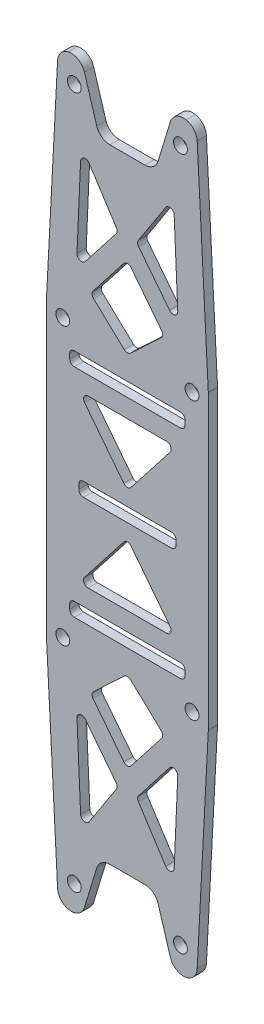
SolidWorks part; units mm, degrees
ref_plane "Alzado" through (0, 0, 0) normal (0, 0, 1) x (1, 0, 0)
ref_plane "Planta" through (0, 0, 0) normal (0, 1, 0) x (1, 0, 0)
ref_plane "Vista lateral" through (0, 0, 0) normal (1, 0, 0) x (0, 0, -1)
sketch "Croquis1" plane through (0, 0, 0) normal (0, 0, 1) x (1, 0, 0)
  line L0 (0, 0) -> (27.8544, 27.8544) construction
  line L1 (0, 0) -> (-42.4264, 42.4264) construction
  line L2 (0, 0) -> (0, 42.4264) construction
  line L3 (15.25, -15.25) -> (-15.25, -15.25) construction
  line L4 (15.25, -15.25) -> (15.25, 15.25) construction
  line L5 (15.25, 15.25) -> (-15.25, 15.25) construction
  line L6 (-15.25, -15.25) -> (-15.25, 15.25) construction
  line L7 (15.25, -15.25) -> (-15.25, 15.25) construction
  line L8 (15.25, 15.25) -> (-15.25, -15.25) construction
  line L9 (0, 42.4264) -> (-20, 42.4264) construction
  line L10 (-42.4264, 42.4264) -> (-38.8909, 45.9619) construction
  line L11 (-38.8909, 45.9619) -> (-31.0962, 38.1673) construction
  line L13 (-42.4264, 42.4264) -> (-45.9619, 38.8909) construction
  line L14 (-45.9619, 38.8909) -> (-38.1673, 31.0962) construction
  line L16 (38.8909, 45.9619) -> (31.0962, 38.1673) construction
  line L17 (42.4264, 42.4264) -> (38.8909, 45.9619) construction
  line L18 (42.4264, 42.4264) -> (45.9619, 38.8909) construction
  line L19 (-45.9619, -38.8909) -> (-38.1673, -31.0962) construction
  line L20 (0, 0) -> (-15.25, 0) construction
  line L21 (45.9619, 38.8909) -> (38.1673, 31.0962) construction
  line L22 (42.4264, -42.4264) -> (45.9619, -38.8909) construction
  line L23 (42.4264, -42.4264) -> (38.8909, -45.9619) construction
  line L24 (38.8909, -45.9619) -> (31.0962, -38.1673) construction
  line L27 (-38.8909, -45.9619) -> (-31.0962, -38.1673) construction
  line L28 (-42.4264, -42.4264) -> (-38.8909, -45.9619) construction
  line L29 (-42.4264, -42.4264) -> (-45.9619, -38.8909) construction
  line L30 (45.9619, -38.8909) -> (38.1673, -31.0962) construction
  line L31 (-15, 80) -> (15, 80) construction
  line L32 (0, -15.25) -> (0, -80) construction
  line L36 (-15, -80) -> (15, -80) construction
  line L41 (-12.268, -54) -> (-12.268, -67.5) construction
  line L43 (-10.268, -54) -> (-10.268, -67.5) construction
  line L105 (0, -80) -> (0, -83) construction
  line L106 (-15, -80) -> (0, -83) construction
  line L127 (15, -80) -> (0, -83) construction
  line L131 (0, 80) -> (0, 83) construction
  line L132 (-15, 80) -> (15, 80) construction
  line L136 (15, 80) -> (0, 83) construction
  line L157 (-15, 80) -> (0, 83) construction
  line L160 (-14, 30) -> (-17.8891, 33.8891) construction
  line L161 (-31.0962, 38.1673) -> (-22.6531, 29.7242) construction
  line L162 (-17.5359, 31.6883) -> (-15, 80) construction
  line L163 (17.5359, 31.6883) -> (15, 80) construction
  line L164 (31.0962, 38.1673) -> (22.6531, 29.7242) construction
  line L165 (31.0962, -38.1673) -> (22.6531, -29.7242) construction
  line L166 (17.5359, -31.6883) -> (15, -80) construction
  line L167 (-17.5359, -31.6883) -> (-15, -80) construction
  line L168 (-31.0962, -38.1673) -> (-22.6531, -29.7242) construction
  line L169 (-8.268, -54) -> (-8.268, -67.5) construction
  line L170 (-6.268, -54) -> (-6.268, -67.5) construction
  line L171 (-4.268, -54) -> (-4.268, -67.5) construction
  line L172 (-2.268, -54) -> (-2.268, -67.5) construction
  line L173 (-8.268, -35) -> (-8.268, -48.5) construction
  line L174 (-6.268, -35) -> (-6.268, -48.5) construction
  line L175 (-4.268, -35) -> (-4.268, -48.5) construction
  line L176 (-2.268, -35) -> (-2.268, -48.5) construction
  line L177 (-12.268, -35) -> (-12.268, -48.5) construction
  line L178 (-10.268, -35) -> (-10.268, -48.5) construction
  line L179 (10.268, -35) -> (10.268, -48.5) construction
  line L180 (12.268, -35) -> (12.268, -48.5) construction
  line L181 (2.268, -35) -> (2.268, -48.5) construction
  line L182 (4.268, -35) -> (4.268, -48.5) construction
  line L183 (6.268, -35) -> (6.268, -48.5) construction
  line L184 (8.268, -35) -> (8.268, -48.5) construction
  line L185 (2.268, -54) -> (2.268, -67.5) construction
  line L186 (4.268, -54) -> (4.268, -67.5) construction
  line L187 (6.268, -54) -> (6.268, -67.5) construction
  line L188 (8.268, -54) -> (8.268, -67.5) construction
  line L189 (10.268, -54) -> (10.268, -67.5) construction
  line L190 (12.268, -54) -> (12.268, -67.5) construction
  line L191 (12.268, 54) -> (12.268, 67.5) construction
  line L192 (10.268, 54) -> (10.268, 67.5) construction
  line L193 (8.268, 54) -> (8.268, 67.5) construction
  line L194 (6.268, 54) -> (6.268, 67.5) construction
  line L195 (4.268, 54) -> (4.268, 67.5) construction
  line L196 (2.268, 54) -> (2.268, 67.5) construction
  line L197 (8.268, 35) -> (8.268, 48.5) construction
  line L198 (6.268, 35) -> (6.268, 48.5) construction
  line L199 (4.268, 35) -> (4.268, 48.5) construction
  line L200 (2.268, 35) -> (2.268, 48.5) construction
  line L201 (12.268, 35) -> (12.268, 48.5) construction
  line L202 (10.268, 35) -> (10.268, 48.5) construction
  line L203 (-10.268, 35) -> (-10.268, 48.5) construction
  line L204 (-12.268, 35) -> (-12.268, 48.5) construction
  line L205 (-2.268, 35) -> (-2.268, 48.5) construction
  line L206 (-4.268, 35) -> (-4.268, 48.5) construction
  line L207 (-6.268, 35) -> (-6.268, 48.5) construction
  line L208 (-8.268, 35) -> (-8.268, 48.5) construction
  line L209 (-2.268, 54) -> (-2.268, 67.5) construction
  line L210 (-4.268, 54) -> (-4.268, 67.5) construction
  line L211 (-6.268, 54) -> (-6.268, 67.5) construction
  line L212 (-8.268, 54) -> (-8.268, 67.5) construction
  line L213 (-10.268, 54) -> (-10.268, 67.5) construction
  line L214 (-12.268, 54) -> (-12.268, 67.5) construction
  line L215 (-0.621, -15.7817) -> (-8.2129, -22.282) construction
  line L216 (-7.5625, -24.0416) -> (8.3607, -24.0416) construction
  line L217 (8.9758, -22.2532) -> (0.6445, -15.7529) construction
  line L218 (-7.5625, 24.0416) -> (8.3607, 24.0416) construction
  line L219 (8.9758, 22.2532) -> (0.6445, 15.7529) construction
  line L220 (-0.621, 15.7817) -> (-8.2129, 22.282) construction
  line L221 (-38.1673, 31.0962) -> (-28.2843, 21.2132) construction
  line L222 (-28.2843, -21.2132) -> (-38.1673, -31.0962) construction
  line L223 (28.2843, -21.2132) -> (38.1673, -31.0962) construction
  line L224 (38.1673, 31.0962) -> (28.2843, 21.2132) construction
  line L225 (-17.5359, 31.6883) -> (-15, 80)
  line L226 (-15, 80) -> (0, 83)
  line L227 (0, 83) -> (15, 80)
  line L228 (15, 80) -> (17.5359, 31.6883)
  line L229 (17.5359, 31.6883) -> (17.5359, -31.6883)
  line L230 (17.5359, -31.6883) -> (15, -80)
  line L231 (15, -80) -> (0, -83)
  line L232 (0, -83) -> (-15, -80)
  line L233 (-15, -80) -> (-17.5359, -31.6883)
  line L234 (-17.5359, -31.6883) -> (-17.5359, 31.6883)
  circle A0 centre (-15.25, 15.25) radius 4 construction
  circle A1 centre (-24.0416, 24.0416) radius 1.5 construction
  circle A2 centre (-38.8909, 38.8909) radius 1.5 construction
  circle A5 centre (38.8909, 38.8909) radius 1.5 construction
  circle A6 centre (24.0416, 24.0416) radius 1.5 construction
  circle A7 centre (15.25, 15.25) radius 4 construction
  circle A8 centre (15.25, -15.25) radius 4 construction
  circle A9 centre (24.0416, -24.0416) radius 1.5 construction
  circle A10 centre (38.8909, -38.8909) radius 1.5 construction
  circle A12 centre (-15.25, -15.25) radius 4 construction
  circle A13 centre (-24.0416, -24.0416) radius 1.5 construction
  circle A14 centre (-38.8909, -38.8909) radius 1.5 construction
  circle A18 centre (0, 0) radius 3.5 construction
  circle A19 centre (-11.5, -75) radius 1.5 construction
  circle A21 centre (-14, 30) radius 1.5 construction
  arc A27 (-12.268, -54) -> (-10.268, -54) centre (-11.268, -54) cw construction
  arc A28 (-12.268, -67.5) -> (-10.268, -67.5) centre (-11.268, -67.5) ccw construction
  circle A111 centre (11.5, -75) radius 1.5 construction
  circle A112 centre (11.5, 75) radius 1.5 construction
  circle A137 centre (-11.5, 75) radius 1.5 construction
  arc A138 (-22.6531, 29.7242) -> (-17.5359, 31.6883) centre (-20.5318, 31.8455) ccw construction
  arc A139 (22.6531, 29.7242) -> (17.5359, 31.6883) centre (20.5318, 31.8455) cw construction
  arc A140 (22.6531, -29.7242) -> (17.5359, -31.6883) centre (20.5318, -31.8455) ccw construction
  arc A141 (-22.6531, -29.7242) -> (-17.5359, -31.6883) centre (-20.5318, -31.8455) cw construction
  circle A142 centre (14, 30) radius 1.5 construction
  circle A143 centre (14, -30) radius 1.5 construction
  circle A144 centre (-14, -30) radius 1.5 construction
  arc A145 (-8.268, -67.5) -> (-6.268, -67.5) centre (-7.268, -67.5) ccw construction
  arc A146 (-8.268, -54) -> (-6.268, -54) centre (-7.268, -54) cw construction
  arc A147 (-4.268, -67.5) -> (-2.268, -67.5) centre (-3.268, -67.5) ccw construction
  arc A148 (-4.268, -54) -> (-2.268, -54) centre (-3.268, -54) cw construction
  arc A149 (-8.268, -48.5) -> (-6.268, -48.5) centre (-7.268, -48.5) ccw construction
  arc A150 (-8.268, -35) -> (-6.268, -35) centre (-7.268, -35) cw construction
  arc A151 (-4.268, -48.5) -> (-2.268, -48.5) centre (-3.268, -48.5) ccw construction
  arc A152 (-4.268, -35) -> (-2.268, -35) centre (-3.268, -35) cw construction
  arc A153 (-12.268, -48.5) -> (-10.268, -48.5) centre (-11.268, -48.5) ccw construction
  arc A154 (-12.268, -35) -> (-10.268, -35) centre (-11.268, -35) cw construction
  arc A155 (12.268, -35) -> (10.268, -35) centre (11.268, -35) ccw construction
  arc A156 (12.268, -48.5) -> (10.268, -48.5) centre (11.268, -48.5) cw construction
  arc A157 (4.268, -35) -> (2.268, -35) centre (3.268, -35) ccw construction
  arc A158 (4.268, -48.5) -> (2.268, -48.5) centre (3.268, -48.5) cw construction
  arc A159 (8.268, -35) -> (6.268, -35) centre (7.268, -35) ccw construction
  arc A160 (8.268, -48.5) -> (6.268, -48.5) centre (7.268, -48.5) cw construction
  arc A161 (4.268, -54) -> (2.268, -54) centre (3.268, -54) ccw construction
  arc A162 (4.268, -67.5) -> (2.268, -67.5) centre (3.268, -67.5) cw construction
  arc A163 (8.268, -54) -> (6.268, -54) centre (7.268, -54) ccw construction
  arc A164 (8.268, -67.5) -> (6.268, -67.5) centre (7.268, -67.5) cw construction
  arc A165 (12.268, -67.5) -> (10.268, -67.5) centre (11.268, -67.5) cw construction
  arc A166 (12.268, -54) -> (10.268, -54) centre (11.268, -54) ccw construction
  arc A167 (12.268, 54) -> (10.268, 54) centre (11.268, 54) cw construction
  arc A168 (12.268, 67.5) -> (10.268, 67.5) centre (11.268, 67.5) ccw construction
  arc A169 (8.268, 67.5) -> (6.268, 67.5) centre (7.268, 67.5) ccw construction
  arc A170 (8.268, 54) -> (6.268, 54) centre (7.268, 54) cw construction
  arc A171 (4.268, 67.5) -> (2.268, 67.5) centre (3.268, 67.5) ccw construction
  arc A172 (4.268, 54) -> (2.268, 54) centre (3.268, 54) cw construction
  arc A173 (8.268, 48.5) -> (6.268, 48.5) centre (7.268, 48.5) ccw construction
  arc A174 (8.268, 35) -> (6.268, 35) centre (7.268, 35) cw construction
  arc A175 (4.268, 48.5) -> (2.268, 48.5) centre (3.268, 48.5) ccw construction
  arc A176 (4.268, 35) -> (2.268, 35) centre (3.268, 35) cw construction
  arc A177 (12.268, 48.5) -> (10.268, 48.5) centre (11.268, 48.5) ccw construction
  arc A178 (12.268, 35) -> (10.268, 35) centre (11.268, 35) cw construction
  arc A179 (-12.268, 35) -> (-10.268, 35) centre (-11.268, 35) ccw construction
  arc A180 (-12.268, 48.5) -> (-10.268, 48.5) centre (-11.268, 48.5) cw construction
  arc A181 (-4.268, 35) -> (-2.268, 35) centre (-3.268, 35) ccw construction
  arc A182 (-4.268, 48.5) -> (-2.268, 48.5) centre (-3.268, 48.5) cw construction
  arc A183 (-8.268, 35) -> (-6.268, 35) centre (-7.268, 35) ccw construction
  arc A184 (-8.268, 48.5) -> (-6.268, 48.5) centre (-7.268, 48.5) cw construction
  arc A185 (-4.268, 54) -> (-2.268, 54) centre (-3.268, 54) ccw construction
  arc A186 (-4.268, 67.5) -> (-2.268, 67.5) centre (-3.268, 67.5) cw construction
  arc A187 (-8.268, 54) -> (-6.268, 54) centre (-7.268, 54) ccw construction
  arc A188 (-8.268, 67.5) -> (-6.268, 67.5) centre (-7.268, 67.5) cw construction
  arc A189 (-12.268, 67.5) -> (-10.268, 67.5) centre (-11.268, 67.5) cw construction
  arc A190 (-12.268, 54) -> (-10.268, 54) centre (-11.268, 54) ccw construction
  arc A191 (8.3607, -24.0416) -> (8.9758, -22.2532) centre (8.3607, -23.0416) ccw construction
  arc A192 (0.6445, -15.7529) -> (-0.621, -15.7817) centre (0.0294, -16.5413) ccw construction
  arc A193 (-8.2129, -22.282) -> (-7.5625, -24.0416) centre (-7.5625, -23.0416) ccw construction
  arc A194 (8.3607, 24.0416) -> (8.9758, 22.2532) centre (8.3607, 23.0416) cw construction
  arc A195 (0.6445, 15.7529) -> (-0.621, 15.7817) centre (0.0294, 16.5413) cw construction
  arc A196 (-8.2129, 22.282) -> (-7.5625, 24.0416) centre (-7.5625, 23.0416) cw construction
  arc A197 (-28.2843, 21.2132) -> (-28.2843, -21.2132) centre (-49.4975, 0) cw construction
  arc A198 (28.2843, 21.2132) -> (28.2843, -21.2132) centre (49.4975, 0) ccw construction
  circle A199 centre (-11.5, 75) radius 1.5
  circle A200 centre (11.5, 75) radius 1.5
  circle A201 centre (14, 30) radius 1.5
  circle A202 centre (-14, 30) radius 1.5
  circle A203 centre (-14, -30) radius 1.5
  circle A204 centre (14, -30) radius 1.5
  circle A205 centre (-11.5, -75) radius 1.5
  circle A206 centre (11.5, -75) radius 1.5
  point P35 (-34.9935, 42.0646)
  point P37 (44.1942, 40.6586)
  point P45 (44.1942, -40.6586)
  point P52 (-16.268, -55.8441)
  point P61 (-34.9935, -42.0646)
  point P70 (0, 80)
  point P260 (-7.0711, 0)
  dimension "D2" = 8
  dimension "D4" = 5
  dimension "D8" = 14.75
  dimension "D10" = 3
  dimension "D11" = 3
  dimension "D13" = 11.5
  dimension "D15" = 3
  dimension "D16" = 14
  dimension "D18" = 3
  dimension "D24" = 3
  dimension "D26" = 1
  dimension "D27" = 7
  dimension "D28" = 30
  dimension "D1" = 30.5
  dimension "D3" = 60
  dimension "D5" = 21
  dimension "D6" = 15
  dimension "D7" = 5
  dimension "D9" = 5
  dimension "D12" = 80
  dimension "D14" = 5
  dimension "D17" = 4
  dimension "D19" = 2
  dimension "D20" = 13.5
  dimension "D21" = 7.5
  dimension "D22" = 3
  dimension "D25" = 2
  dimension "D23" = 5.5
extrude "Saliente-Extruir1" add sketch "Croquis1" along normal blind 2
sketch "Croquis2" plane through (0, 0, 2) normal (0, 0, 1) x (1, 0, 0)
  line L1 (0, 83) -> (-15, 80) construction
  line L2 (-7.5, 81.5) -> (7.5, 81.5) construction
  line L3 (15, 80) -> (0, 83) construction
  line L4 (7.5, 81.5) -> (15, 80) construction
  line L5 (0, 81.5) -> (0, 67.5) construction
  line L6 (-10, 75) -> (-8.2794, 75) construction
  line L7 (-10.0971, 80.9806) -> (-8.2794, 75) construction
  line L8 (-10.0971, 80.9806) -> (-6, 67.5)
  line L9 (-6, 67.5) -> (6, 67.5)
  line L10 (-10.0971, 80.9806) -> (0, 83)
  line L11 (10.0971, 80.9806) -> (6, 67.5)
  line L12 (10.0971, 80.9806) -> (0, 83)
  line L13 (-10, 75) -> (-10, 64.4328) construction
  line L14 (-10, 64.4328) -> (-11.0513, 40.4559)
  line L15 (0, 67.5) -> (0, 30) construction
  line L16 (-10.5257, 52.4444) -> (0, 51.9828) construction
  line L17 (0, 51.9828) -> (-2, 52.0705) construction
  line L18 (0, 30) -> (0, 37.5) construction
  line L19 (-11.0513, 40.4559) -> (-2, 52.0705)
  line L20 (-2, 52.0705) -> (-10, 64.4328)
  line L21 (2, 52.0705) -> (10, 64.4328)
  line L22 (10, 64.4328) -> (11.0513, 40.4559)
  line L23 (11.0513, 40.4559) -> (2, 52.0705)
  line L24 (-12.5, 30) -> (12.5, 30) construction
  line L25 (0, 37.5) -> (-8, 37.5) construction
  line L26 (0, 30) -> (-8, 37.5)
  line L27 (-8, 37.5) -> (0, 47.7656)
  line L28 (0, 30) -> (8, 37.5)
  line L29 (8, 37.5) -> (0, 47.7656)
  line L30 (-17.5359, 0) -> (17.5359, 0) construction
  line L31 (-17.5359, 31.6883) -> (-17.5359, -31.6883) construction
  line L32 (17.5359, -31.6883) -> (17.5359, 31.6883) construction
  line L33 (-10.5359, 18) -> (10.5359, 18)
  line L34 (-12.5, 25) -> (12.5, 25)
  line L35 (-12.5, 25) -> (-12.5, 22)
  line L36 (-12.5, 22) -> (12.5, 22)
  line L37 (12.5, 25) -> (12.5, 22)
  line L38 (-10.5359, -1.5) -> (-10.5359, 1.5)
  line L39 (-10.5359, 1.5) -> (10.5359, 1.5)
  line L40 (10.5359, 1.5) -> (10.5359, -1.5)
  line L41 (0, 1.5) -> (0, 4.5) construction
  line L42 (-10.5359, 18) -> (0, 4.5)
  line L43 (0, 4.5) -> (10.5359, 18)
  line L44 (0, -1.5) -> (0, -4.5) construction
  line L45 (0, -37.5) -> (-8, -37.5) construction
  line L46 (-12.5, -30) -> (12.5, -30) construction
  line L47 (0, -30) -> (0, -37.5) construction
  line L48 (0, -51.9828) -> (-2, -52.0705) construction
  line L49 (-10.5257, -52.4444) -> (0, -51.9828) construction
  line L50 (0, -67.5) -> (0, -30) construction
  line L51 (-10, -75) -> (-10, -64.4328) construction
  line L52 (-10.0971, -80.9806) -> (-8.2794, -75) construction
  line L53 (-10, -75) -> (-8.2794, -75) construction
  line L54 (0, -81.5) -> (0, -67.5) construction
  line L55 (7.5, -81.5) -> (15, -80) construction
  line L56 (-7.5, -81.5) -> (7.5, -81.5) construction
  line L57 (-15, -80) -> (-7.5, -81.5) construction
  line L58 (0, -4.5) -> (10.5359, -18)
  line L59 (-10.5359, -18) -> (0, -4.5)
  line L60 (-10.5359, -1.5) -> (10.5359, -1.5)
  line L61 (12.5, -25) -> (12.5, -22)
  line L62 (-12.5, -22) -> (12.5, -22)
  line L63 (-12.5, -25) -> (-12.5, -22)
  line L64 (-12.5, -25) -> (12.5, -25)
  line L65 (-10.5359, -18) -> (10.5359, -18)
  line L66 (8, -37.5) -> (0, -47.7656)
  line L67 (0, -30) -> (8, -37.5)
  line L68 (-8, -37.5) -> (0, -47.7656)
  line L69 (0, -30) -> (-8, -37.5)
  line L70 (11.0513, -40.4559) -> (2, -52.0705)
  line L71 (10, -64.4328) -> (11.0513, -40.4559)
  line L72 (2, -52.0705) -> (10, -64.4328)
  line L73 (-2, -52.0705) -> (-10, -64.4328)
  line L74 (-11.0513, -40.4559) -> (-2, -52.0705)
  line L75 (-10, -64.4328) -> (-11.0513, -40.4559)
  line L76 (10.0971, -80.9806) -> (0, -83)
  line L77 (10.0971, -80.9806) -> (6, -67.5)
  line L78 (-10.0971, -80.9806) -> (0, -83)
  line L79 (-6, -67.5) -> (6, -67.5)
  line L80 (-10.0971, -80.9806) -> (-6, -67.5)
  circle A0 centre (-11.5, 75) radius 1.5 construction
  circle A1 centre (-14, 30) radius 1.5 construction
  circle A2 centre (14, 30) radius 1.5 construction
  point P85 (10.5359, 0)
  point P86 (-10.5359, 0)
  dimension "D1" = 14
  dimension "D2" = 12
  dimension "D3" = 8
  dimension "D4" = 2
  dimension "D5" = 7.5
  dimension "D6" = 5
  dimension "D7" = 3
  dimension "D8" = 4
  dimension "D9" = 1.5
  dimension "D10" = 7
  dimension "D11" = 7
  dimension "D12" = 3
  dimension "D13" = 6
  dimension "D14" = 5
extrude "Cortar-Extruir1" cut sketch "Croquis2" against normal up to vertex (2 mm away) up to point (-17.5359, -31.6883, 0)
fillet "Redondeo2" radius 1 38 edges at (0, -30, 1) (11.0513, -40.4559, 1) (10, -64.4328, 1) (2, -52.0705, 1) (-10, -64.4328, 1) (-8, -37.5, 1) (8, -37.5, 1) (-2, -52.0705, 1) (-11.0513, -40.4559, 1) (12.5, 22, 1) (-12.5, 22, 1) (-12.5, 25, 1) (12.5, 25, 1) (10.5359, 18, 1) (-10.5359, 18, 1) (0, 4.5, 1) (10.5359, -1.5, 1) (-10.5359, -1.5, 1) (10.5359, 1.5, 1) (-10.5359, 1.5, 1) (10.5359, -18, 1) (0, -4.5, 1) (-10.5359, -18, 1) (12.5, -25, 1) (-12.5, -25, 1) (12.5, -22, 1) (-12.5, -22, 1) (0, 30, 1) (8, 37.5, 1) (-8, 37.5, 1) (0, 47.7656, 1) (11.0513, 40.4559, 1) (10, 64.4328, 1) (2, 52.0705, 1) (-2, 52.0705, 1) (-11.0513, 40.4559, 1) (-10, 64.4328, 1) (0, -47.7656, 1)
fillet "Redondeo1" radius 3 16 edges at (15, -80, 1) (-15, -80, 1) (15, 80, 1) (-15, 80, 1) (-6, -67.5, 1) (6, -67.5, 1) (10.0971, -80.9806, 1) (-10.0971, -80.9806, 1) (10.0971, 80.9806, 1) (6, 67.5, 1) (-6, 67.5, 1) (-10.0971, 80.9806, 1) (17.5359, -31.6883, 1) (17.5359, 31.6883, 1) (-17.5359, -31.6883, 1) (-17.5359, 31.6883, 1)
sketch "Croquis3" plane through (0, 0, 2) normal (0, 0, 1) x (1, 0, 0)
  line L0 (0, 30.3707) -> (0, 67.5) construction
  line L2 (-11.5, 40) -> (-11.5, 37)
  line L4 (-9.5, 40) -> (-9.5, 37)
  line L5 (-3.7763, 67.5) -> (3.7763, 67.5) construction
  line L6 (9.5, 40) -> (9.5, 37)
  line L7 (11.5, 40) -> (11.5, 37)
  line L8 (9.5, 67) -> (9.5, 64)
  line L9 (11.5, 67) -> (11.5, 64)
  line L10 (-11.5, 67) -> (-11.5, 64)
  line L11 (-9.5, 67) -> (-9.5, 64)
  line L12 (0, 0) -> (17.5359, 0) construction
  line L13 (17.5359, -31.6096) -> (17.5359, 31.6096) construction
  line L14 (0, -30.3707) -> (0, -67.5) construction
  line L15 (-9.5, -67) -> (-9.5, -64)
  line L16 (-11.5, -67) -> (-11.5, -64)
  line L17 (11.5, -67) -> (11.5, -64)
  line L18 (9.5, -67) -> (9.5, -64)
  line L19 (11.5, -40) -> (11.5, -37)
  line L20 (9.5, -40) -> (9.5, -37)
  line L21 (-9.5, -40) -> (-9.5, -37)
  line L22 (-11.5, -40) -> (-11.5, -37)
  arc A0 (-0.6839, 30.6412) -> (0.6839, 30.6412) centre (0, 31.3707) ccw construction
  arc A1 (-11.5, 37) -> (-9.5, 37) centre (-10.5, 37) ccw
  arc A2 (-11.5, 40) -> (-9.5, 40) centre (-10.5, 40) cw
  arc A3 (9.5, 37) -> (11.5, 37) centre (10.5, 37) ccw
  arc A4 (9.5, 40) -> (11.5, 40) centre (10.5, 40) cw
  arc A5 (9.5, 64) -> (11.5, 64) centre (10.5, 64) ccw
  arc A6 (9.5, 67) -> (11.5, 67) centre (10.5, 67) cw
  arc A7 (-11.5, 64) -> (-9.5, 64) centre (-10.5, 64) ccw
  arc A8 (-11.5, 67) -> (-9.5, 67) centre (-10.5, 67) cw
  arc A9 (-11.5, -67) -> (-9.5, -67) centre (-10.5, -67) ccw
  arc A10 (-11.5, -64) -> (-9.5, -64) centre (-10.5, -64) cw
  arc A11 (9.5, -67) -> (11.5, -67) centre (10.5, -67) ccw
  arc A12 (9.5, -64) -> (11.5, -64) centre (10.5, -64) cw
  arc A13 (9.5, -40) -> (11.5, -40) centre (10.5, -40) ccw
  arc A14 (9.5, -37) -> (11.5, -37) centre (10.5, -37) cw
  arc A15 (-11.5, -40) -> (-9.5, -40) centre (-10.5, -40) ccw
  arc A16 (-11.5, -37) -> (-9.5, -37) centre (-10.5, -37) cw
  dimension "D1" = 3
  dimension "D2" = 2
  dimension "D3" = 9.5
  dimension "D4" = 37
  dimension "D7" = 24
  dimension "D5" = 2
  dimension "D6" = 2
sketch "Croquis4" plane through (0, 0, 2) normal (0, 0, 1) x (1, 0, 0)
  line L0 (-15.1222, -77.6726) -> (-16.327, -54.7197)
  line L1 (-17.5318, -31.7668) -> (-15.1222, -77.6726) construction
  line L2 (15.1222, -77.6726) -> (16.327, -54.7197)
  line L3 (15.1222, -77.6726) -> (17.5318, -31.7668) construction
  line L4 (16.327, -54.7197) -> (-16.327, -54.7197)
  line L5 (-9.306, -78.3777) -> (-6.6466, -69.6276)
  line L6 (-3.7763, -67.5) -> (3.7763, -67.5)
  line L7 (6.6466, -69.6276) -> (9.306, -78.3777)
  circle A1 centre (11.5, -75) radius 1.5
  arc A2 (-12.7397, -80.452) -> (-15.1222, -77.6726) centre (-12.1263, -77.5153) cw
  arc A3 (-12.7397, -80.452) -> (-9.306, -78.3777) centre (-12.1764, -77.5053) ccw
  arc A4 (-6.6466, -69.6276) -> (-3.7763, -67.5) centre (-3.7763, -70.5) cw
  arc A5 (3.7763, -67.5) -> (6.6466, -69.6276) centre (3.7763, -70.5) cw
  arc A6 (9.306, -78.3777) -> (12.7397, -80.452) centre (12.1764, -77.5053) ccw
  arc A7 (12.7397, -80.452) -> (15.1222, -77.6726) centre (12.1263, -77.5153) ccw
  circle A8 centre (-11.5, -75) radius 1.5
extrude "Cortar-Extruir2" [suppressed] cut sketch "Croquis3" against normal blind 10
